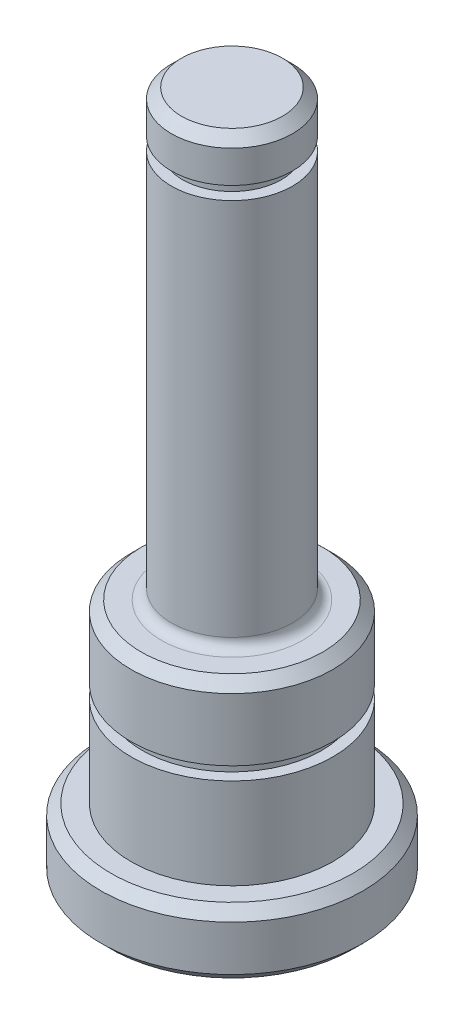
SolidWorks part; units mm, degrees
ref_plane "Front Plane" through (0, 0, 0) normal (0, 0, 1) x (1, 0, 0)
ref_plane "Top Plane" through (0, 0, 0) normal (0, 1, 0) x (1, 0, 0)
ref_plane "Right Plane" through (0, 0, 0) normal (1, 0, 0) x (0, 0, -1)
ref_axis "X" through (88.99, 0, 0) along (-1, 0, 0)
ref_axis "Y" through (0, 55, 0) along (0, -1, 0)
ref_axis "Z" through (0, 0, -88.99) along (0, 0, 1)
sketch "Sketch1" plane through (0, 0, 0) normal (0, 0, 1) x (1, 0, 0)
  line L0 (0, 0) -> (-13, 0) construction
  line L1 (0, 0) -> (0, 68) construction
  line L2 (-5, 0) -> (-13, 0)
  line L3 (-10, 6.5) -> (-10, 15.5)
  line L4 (-10, 24) -> (-6, 24)
  line L5 (-6, 24) -> (-6, 62.5)
  line L6 (-6, 68) -> (0, 68)
  line L7 (0, 68) -> (0, 18)
  line L8 (0, 18) -> (-5, 18)
  line L9 (-5, 18) -> (-5, 0)
  line L10 (-13, 0) -> (-13, 6.5)
  line L11 (-13, 6.5) -> (-10, 6.5)
  line L12 (-10, 24) -> (-10, 16.8)
  line L13 (-10, 15.5) -> (-8.9, 15.5)
  line L15 (-10, 16.8) -> (-8.9, 16.8)
  line L16 (-8.9, 15.5) -> (-8.9, 16.8)
  line L17 (-6, 63.8) -> (-6, 68)
  line L18 (-6, 62.5) -> (-4.9, 62.5)
  line L20 (-6, 63.8) -> (-4.9, 63.8)
  line L21 (-4.9, 62.5) -> (-4.9, 63.8)
  dimension "D1" = 12
  dimension "D2" = 20
  dimension "D3" = 10
  dimension "D4" = 18
  dimension "D5" = 24
  dimension "D6" = 68
  dimension "D7" = 6.5
  dimension "D8" = 26
  dimension "D9" = 9
  dimension "D10" = 1.3
  dimension "D11" = 1.1
  dimension "D12" = 10
  dimension "D13" = 38.5
  dimension "D14" = 1.3
  dimension "D15" = 1.1
revolve "Revolve1" add sketch "Sketch1" angle 360 about L1
chamfer "Chamfer1" distance 1 angle 45 5 edges at (5, 0, 0) (13, 0, 0) (13, 6.5, 0) (10, 24, 0) (6, 68, 0)
fillet "Fillet2" radius 1 1 edges at (6, 24, 0)
